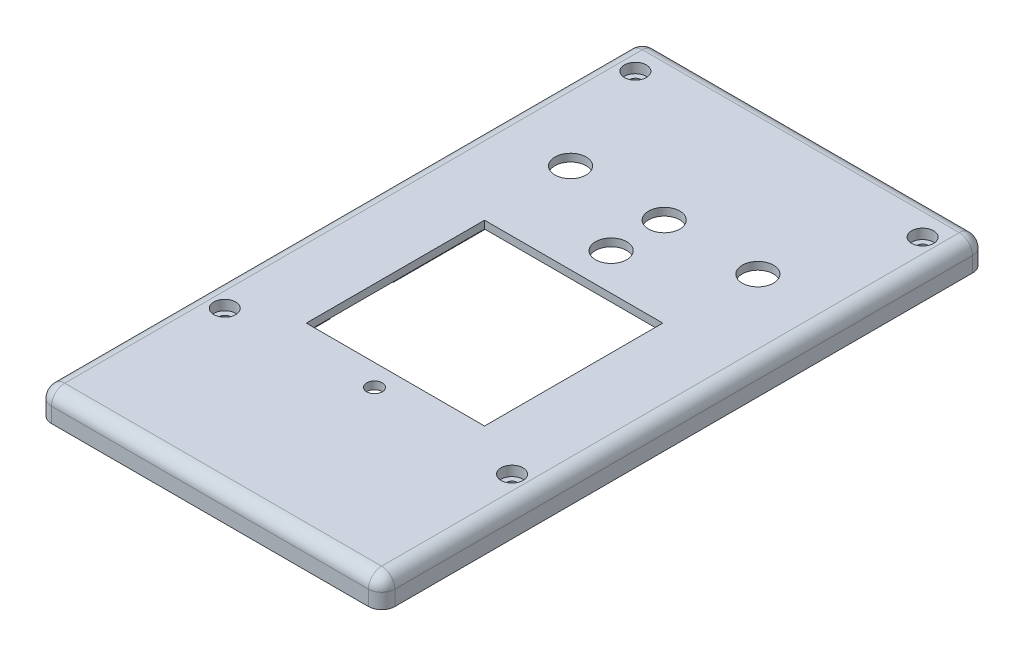
SolidWorks part; units mm, degrees
ref_plane "Face" through (0, 0, 0) normal (0, 0, 1) x (1, 0, 0)
ref_plane "Dessus" through (0, 0, 0) normal (0, 1, 0) x (1, 0, 0)
ref_plane "Droite" through (0, 0, 0) normal (1, 0, 0) x (0, 0, -1)
sketch "Sketch1" plane through (0, 0, 0) normal (0, 1, 0) x (1, 0, 0)
  line L0 (0, -49.53) -> (0, 0) construction
  line L1 (27.94, -49.53) -> (-27.94, -49.53)
  line L2 (27.94, -49.53) -> (27.94, 48.768)
  line L3 (27.94, 48.768) -> (-27.94, 48.768)
  line L4 (-27.94, -49.53) -> (-27.94, 48.768)
  point P0 (0, 0)
  dimension "D1" = 55.88
  dimension "D2" = 49.53
  dimension "D3" = 48.768
extrude "Boss-Extrude1" add sketch "Sketch1" along normal blind 3.81
fillet "Fillet1" radius 2.159 8 edges at (0, 3.81, 49.53) (27.94, 3.81, 0.381) (0, 3.81, -48.768) (-27.94, 3.81, 0.381) (-27.94, 1.905, -48.768) (27.94, 1.905, -48.768) (27.94, 1.905, 49.53) (-27.94, 1.905, 49.53)
sketch "Sketch3" plane through (0, 0, 0) normal (0, -1, 0) x (1, 0, 0)
  line L1 (21.6281, -38.862) -> (-20.4089, -38.862)
  line L2 (21.6281, -38.862) -> (21.6281, 26.576)
  line L3 (21.6281, 26.576) -> (-20.4089, 26.576)
  line L4 (-20.4089, -38.862) -> (-20.4089, 26.576)
  line L5 (21.6281, -38.862) -> (-20.4089, 26.576) construction
  line L6 (21.6281, 26.576) -> (-20.4089, -38.862) construction
  point P0 (0.6096, -6.143)
  dimension "D1" = 42.037
  dimension "D2" = 26.576
  dimension "D3" = 38.862
  dimension "D4" = 0.6096
sketch "Sketch7" plane through (0, 0, 0) normal (0, -1, 0) x (1, 0, 0)
  line L6 (-25.781, -47.752) -> (25.781, -47.752)
  line L9 (26.924, 47.371) -> (26.924, -46.609)
  line L10 (-26.924, -46.609) -> (-26.924, 47.371)
  line L11 (-25.781, 48.514) -> (25.781, 48.514)
  line L12 (26.924, 47.371) -> (26.924, -46.609)
  line L13 (-26.924, -46.609) -> (-26.924, 47.371)
  line L14 (-25.781, 48.514) -> (25.781, 48.514)
  arc A9 (25.781, -47.752) -> (26.924, -46.609) centre (25.781, -46.609) ccw
  arc A16 (25.781, -47.752) -> (26.924, -46.609) centre (25.781, -46.609) ccw
  arc A17 (-26.924, -46.609) -> (-25.781, -47.752) centre (-25.781, -46.609) ccw
  arc A18 (-26.924, -46.609) -> (-25.781, -47.752) centre (-25.781, -46.609) ccw
  arc A19 (-25.781, 48.514) -> (-26.924, 47.371) centre (-25.781, 47.371) ccw
  arc A20 (-25.781, 48.514) -> (-26.924, 47.371) centre (-25.781, 47.371) ccw
  arc A21 (26.924, 47.371) -> (25.781, 48.514) centre (25.781, 47.371) ccw
  arc A22 (26.924, 47.371) -> (25.781, 48.514) centre (25.781, 47.371) ccw
  dimension "D1" = 1.016
  dimension "D2" = 1.016
extrude "Cut-Extrude4" cut sketch "Sketch7" against normal blind 0.7874
sketch "Sketch8" plane through (0, 0, 0) normal (0, -1, 0) x (1, 0, 0)
  line L0 (27.94, 47.371) -> (27.94, -46.609) construction
  line L2 (26.924, -46.609) -> (26.924, 47.371) construction
  line L3 (-25.781, -47.752) -> (25.781, -47.752) construction
  line L4 (26.924, -46.609) -> (26.924, -40.386)
  line L5 (21.717, -47.752) -> (25.781, -47.752)
  line L6 (21.717, -47.752) -> (21.717, -40.386)
  line L7 (21.717, -40.386) -> (26.924, -40.386)
  circle A0 centre (23.4188, -43.006) radius 0.889
  arc A1 (25.781, -47.752) -> (26.924, -46.609) centre (25.781, -46.609) ccw construction
  arc A2 (25.781, -47.752) -> (26.924, -46.609) centre (25.781, -46.609) ccw
  dimension "D3" = 1.778
  dimension "D1" = 4.5212
  dimension "D2" = 43.006
  dimension "D4" = 6.223
  dimension "D5" = 40.386
sketch "Sketch9" plane through (0, 0, 0) normal (0, -1, 0) x (1, 0, 0)
  line L0 (-26.924, 47.371) -> (-26.924, -46.609) construction
  line L1 (-25.781, -47.752) -> (25.781, -47.752) construction
  line L2 (-26.924, -40.005) -> (-26.924, -46.609)
  line L3 (-25.781, -47.752) -> (-20.447, -47.752)
  line L4 (-20.447, -47.752) -> (-20.447, -40.005)
  line L5 (-20.447, -40.005) -> (-26.924, -40.005)
  line L6 (-27.94, -46.609) -> (-27.94, 47.371) construction
  arc A0 (-26.924, -46.609) -> (-25.781, -47.752) centre (-25.781, -46.609) ccw construction
  arc A1 (-26.924, -46.609) -> (-25.781, -47.752) centre (-25.781, -46.609) ccw
  circle A2 centre (-23.3172, -43.006) radius 0.889
  dimension "D5" = 1.778
  dimension "D1" = 7.493
  dimension "D2" = 43.006
  dimension "D3" = 3.6068
  dimension "D4" = 40.005
sketch "Sketch10" plane through (0, 0, 0) normal (0, -1, 0) x (1, 0, 0)
  line L0 (-27.94, -46.609) -> (-27.94, 47.371) construction
  line L1 (-26.924, 47.371) -> (-26.924, -46.609) construction
  line L2 (-26.924, 17.78) -> (-20.447, 17.78)
  line L3 (-26.924, 17.78) -> (-26.924, 26.67)
  line L4 (-26.924, 26.67) -> (-20.447, 26.67)
  line L5 (-20.447, 17.78) -> (-20.447, 26.67)
  circle A0 centre (-23.3172, 23.796) radius 0.889
  dimension "D6" = 1.778
  dimension "D1" = 4.6228
  dimension "D2" = 23.796
  dimension "D3" = 6.477
  dimension "D4" = 26.67
  dimension "D5" = 17.78
sketch "Sketch11" plane through (0, 0, 0) normal (0, -1, 0) x (1, 0, 0)
  line L0 (26.924, -46.609) -> (26.924, 47.371) construction
  line L1 (26.924, 27.686) -> (21.7502, 27.686)
  line L2 (26.924, 27.686) -> (26.924, 20.32)
  line L3 (26.924, 20.32) -> (21.7502, 20.32)
  line L4 (21.7502, 27.686) -> (21.7502, 20.32)
  circle A0 centre (23.4188, 23.796) radius 0.889
  dimension "D6" = 1.778
  dimension "D1" = 23.796
  dimension "D2" = 23.4188
  dimension "D3" = 27.686
  dimension "D4" = 20.32
  dimension "D5" = 21.7502
sketch "Sketch12" plane through (0, 0.7874, 0) normal (0, -1, 0) x (1, 0, 0)
  line L0 (26.924, -38.1) -> (19.812, -38.1)
  line L1 (-26.924, 27.94) -> (-16.28, 27.94)
  line L3 (-26.924, 13.7274) -> (-16.28, 13.7274)
  line L4 (26.924, -46.609) -> (26.924, 47.371)
  line L5 (25.781, 48.514) -> (-25.781, 48.514)
  line L6 (-26.924, 47.371) -> (-26.924, -46.609)
  line L7 (-25.781, -47.752) -> (25.781, -47.752)
  line L8 (26.924, -38.1) -> (26.924, -17.145)
  line L9 (25.781, 48.514) -> (8.5725, 48.514)
  line L10 (-26.924, 47.371) -> (-26.924, 27.94)
  line L11 (-19.812, -47.752) -> (19.812, -47.752)
  line L12 (-16.28, 27.94) -> (-16.28, 13.7274)
  line L13 (26.924, 27.94) -> (19.812, 27.94)
  line L17 (19.812, -38.1) -> (19.812, -47.752)
  line L18 (-26.924, -38.1) -> (-19.812, -38.1)
  line L19 (-19.812, -38.1) -> (-19.812, -47.752)
  line L20 (-26.924, 3.429) -> (-16.28, 3.429)
  line L21 (-16.28, 3.429) -> (-16.28, -17.145)
  line L22 (-16.28, -17.145) -> (-26.924, -17.145)
  line L25 (19.812, -17.145) -> (26.924, -17.145)
  line L26 (0, 44.704) -> (0, 0) construction
  line L28 (8.5725, 48.514) -> (8.5725, 44.704)
  line L29 (8.5725, 44.704) -> (-8.5725, 44.704)
  line L30 (-8.5725, 48.514) -> (-8.5725, 44.704)
  line L31 (0, 0) -> (0, -47.752) construction
  line L36 (-8.5725, 48.514) -> (-25.781, 48.514)
  line L37 (26.924, 27.94) -> (26.924, 47.371)
  line L38 (-26.924, 13.7274) -> (-26.924, 3.429)
  line L39 (-26.924, -17.145) -> (-26.924, -38.1)
  line L40 (26.924, -3.275) -> (26.924, 12.725)
  line L41 (19.812, -17.145) -> (19.812, -11.275)
  line L42 (19.812, -11.275) -> (22.346, -11.275)
  line L43 (22.346, -11.275) -> (22.346, -3.275)
  line L44 (22.346, -3.275) -> (26.924, -3.275)
  line L45 (19.812, 27.94) -> (19.812, 20.725)
  line L46 (19.812, 20.725) -> (22.346, 20.725)
  line L47 (22.346, 20.725) -> (22.346, 12.725)
  line L48 (22.346, 12.725) -> (26.924, 12.725)
  arc A4 (25.781, -47.752) -> (26.924, -46.609) centre (25.781, -46.609) ccw
  arc A5 (26.924, 47.371) -> (25.781, 48.514) centre (25.781, 47.371) ccw
  arc A6 (-25.781, 48.514) -> (-26.924, 47.371) centre (-25.781, 47.371) ccw
  arc A7 (-26.924, -46.609) -> (-25.781, -47.752) centre (-25.781, -46.609) ccw
  arc A9 (26.924, 47.371) -> (25.781, 48.514) centre (25.781, 47.371) ccw
  arc A10 (-25.781, 48.514) -> (-26.924, 47.371) centre (-25.781, 47.371) ccw
  line M33 (26.924, -46.609) -> (26.924, 47.371)
  arc M34 (26.924, 47.371) -> (25.781, 48.514) centre (25.781, 47.371) ccw
  line M35 (25.781, 48.514) -> (-25.781, 48.514)
  arc M36 (-25.781, 48.514) -> (-26.924, 47.371) centre (-25.781, 47.371) ccw
  line M37 (-26.924, 47.371) -> (-26.924, -46.609)
  line M39 (-25.781, -47.752) -> (25.781, -47.752)
  dimension "D2" = 12.725
  dimension "D3" = 17.145
  dimension "D4" = 3.81
  dimension "D5" = 27.94
  dimension "D6" = 14.2126
  dimension "D7" = 3.429
  dimension "D8" = 17.145
  dimension "D9" = 38.1
  dimension "D10" = 39.624
  dimension "D11" = 16.28
  dimension "D12" = 4.578
  dimension "D13" = 32
  dimension "D14" = 20.725
  dimension "D15" = 16
  dimension "D1" = 0
extrude "Cut-Extrude5" cut sketch "Sketch12" against normal blind 1.778 contours L17 L0 L25 L41 L48 L13 L28 L29 L30 L1 L12 L3 L20 L21 L22 L18 L19 M39 M33 M34 M35 M36 M37 region at (0.9045, 0.7874, 0.4828)
fillet "Fillet4" radius 1.016 11 edges at (26.924, 2.5654, 37.6555) (26.5892, 2.5654, 48.1792) (-26.924, 2.5654, 37.6555) (-26.5892, 2.5654, 48.1792) (0, 2.5654, -47.752) (-26.924, 2.5654, 8.5782) (-26.924, 2.5654, -27.6225) (26.924, 2.5654, -27.6225) (26.924, 2.5654, 4.725) (17.1767, 2.5654, 48.514) (-17.1767, 2.5654, 48.514)
hole_wizard "CBORE for #0 Button Head Cap Screw1" positions "Sketch13" profile "Sketch14" counterbore size "#0" standard "ANSI Inch" end condition through all
sketch "Sketch13" plane through (0, 3.81, 0) normal (0, 1, 0) x (1, 0, 0)
  point P0 (-23.3172, -23.796)
  point P3 (23.4188, -23.796)
  point P6 (23.4188, 43.006)
  point P9 (-23.3172, 43.006)
sketch "Sketch14" plane through (-23.3172, 3.81, 23.796) normal (1, 0, 0) x (0, 0, 1)
  line L0 (0, 0) -> (0, 3.81)
  line L1 (0, 3.81) -> (0.889, 3.81)
  line L3 (0.889, 3.81) -> (0.889, 1.6128)
  line L4 (0.889, 1.6128) -> (1.7856, 1.6128)
  line L5 (1.7856, 1.6128) -> (1.7856, 0)
  line L7 (1.7856, 0) -> (0, 0)
  line L11 (0, -6.35) -> (0, 107.95) construction
  dimension "Thru Hole Dia." = 1.778
  dimension "Thru Hole Depth" = 3.81
  dimension "C'Bore Dia." = 3.5712
  dimension "C'Bore Depth" = 1.6128
sketch "Sketch15" plane through (0, 2.5654, 0) normal (0, -1, 0) x (1, 0, 0)
  line L0 (0, 0) -> (0, -15.748) construction
  line L1 (0, -15.748) -> (0, -24.384) construction
  line L2 (0, -24.384) -> (-15.24, -24.384) construction
  line L3 (0, -24.384) -> (15.24, -24.384) construction
  circle A0 centre (0, -24.384) radius 2.54
  circle A1 centre (-15.24, -24.384) radius 2.54
  circle A2 centre (15.24, -24.384) radius 2.54
  circle A3 centre (0, -15.748) radius 2.54
  dimension "D4" = 5.08
  dimension "D1" = 24.384
  dimension "D2" = 15.748
  dimension "D3" = 30.48
extrude "Cut-Extrude6" cut sketch "Sketch15" against normal through all
sketch "Sketch16" plane through (0, 3.81, 0) normal (0, 1, 0) x (1, 0, 0)
  line L1 (14.4038, -19.2509) -> (-14.5962, -19.2509)
  line L2 (14.4038, -19.2509) -> (14.4038, 9.7491)
  line L3 (14.4038, 9.7491) -> (-14.5962, 9.7491)
  line L4 (-14.5962, -19.2509) -> (-14.5962, 9.7491)
  dimension "D1" = 29
  dimension "D2" = 9.7491
  dimension "D3" = 14.4038
extrude "Cut-Extrude7" cut sketch "Sketch16" against normal through all
sketch "Sketch17" plane through (0, 0, 0) normal (0, -1, 0) x (1, 0, 0)
  line L0 (-25.781, -47.752) -> (25.781, -47.752) construction
  line L1 (26.924, -46.609) -> (26.924, 47.371) construction
  line L2 (25.781, 48.514) -> (-25.781, 48.514) construction
  line L3 (-26.924, 47.371) -> (-26.924, -46.609) construction
  line L4 (-27.94, 47.371) -> (-27.94, -46.609)
  line L5 (-25.781, -48.768) -> (25.781, -48.768)
  line L6 (27.94, -46.609) -> (27.94, 47.371)
  line L7 (25.781, 49.53) -> (-25.781, 49.53)
  line L8 (-27.94, 47.371) -> (-27.94, -46.609)
  line L9 (-25.781, -48.768) -> (25.781, -48.768)
  line L10 (27.94, -46.609) -> (27.94, 47.371)
  line L11 (25.781, 49.53) -> (-25.781, 49.53)
  line L12 (-25.781, -47.752) -> (25.781, -47.752)
  line L13 (26.924, -46.609) -> (26.924, 47.371)
  line L14 (25.781, 48.514) -> (-25.781, 48.514)
  line L15 (-26.924, 47.371) -> (-26.924, -46.609)
  arc A0 (-26.924, -46.609) -> (-25.781, -47.752) centre (-25.781, -46.609) ccw construction
  arc A1 (25.781, -47.752) -> (26.924, -46.609) centre (25.781, -46.609) ccw construction
  arc A2 (26.924, 47.371) -> (25.781, 48.514) centre (25.781, 47.371) ccw construction
  arc A3 (-25.781, 48.514) -> (-26.924, 47.371) centre (-25.781, 47.371) ccw construction
  arc A4 (-27.94, -46.609) -> (-25.781, -48.768) centre (-25.781, -46.609) ccw
  arc A5 (25.781, -48.768) -> (27.94, -46.609) centre (25.781, -46.609) ccw
  arc A6 (27.94, 47.371) -> (25.781, 49.53) centre (25.781, 47.371) ccw
  arc A7 (-25.781, 49.53) -> (-27.94, 47.371) centre (-25.781, 47.371) ccw
  arc A8 (-27.94, -46.609) -> (-25.781, -48.768) centre (-25.781, -46.609) ccw
  arc A9 (25.781, -48.768) -> (27.94, -46.609) centre (25.781, -46.609) ccw
  arc A10 (27.94, 47.371) -> (25.781, 49.53) centre (25.781, 47.371) ccw
  arc A11 (-25.781, 49.53) -> (-27.94, 47.371) centre (-25.781, 47.371) ccw
  arc A12 (-26.924, -46.609) -> (-25.781, -47.752) centre (-25.781, -46.609) ccw
  arc A13 (25.781, -47.752) -> (26.924, -46.609) centre (25.781, -46.609) ccw
  arc A14 (26.924, 47.371) -> (25.781, 48.514) centre (25.781, 47.371) ccw
  arc A15 (-25.781, 48.514) -> (-26.924, 47.371) centre (-25.781, 47.371) ccw
  dimension "D1" = 0
extrude "Boss-Extrude2" add sketch "Sketch17" along normal blind 0.8
sketch "Sketch18" plane through (0, 3.81, 0) normal (0, 1, 0) x (1, 0, 0)
  line L0 (0, 0) -> (0, -22.752) construction
  circle A0 centre (0, -22.752) radius 1.27
  dimension "D1" = 2.54
  dimension "D2" = 22.752
extrude "Cut-Extrude8" cut sketch "Sketch18" against normal through all
